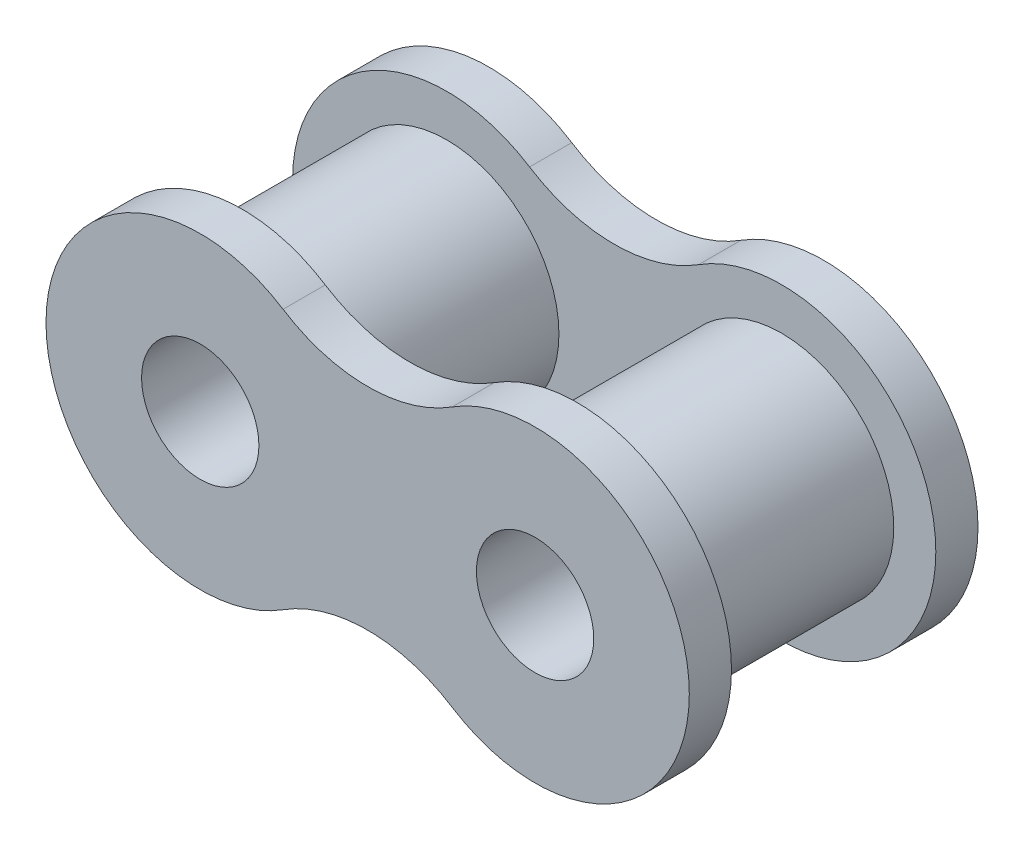
SolidWorks part; units mm, degrees
ref_plane "Front Plane" through (0, 0, 0) normal (0, 0, 1) x (1, 0, 0)
ref_plane "Top Plane" through (0, 0, 0) normal (0, 1, 0) x (1, 0, 0)
ref_plane "Right Plane" through (0, 0, 0) normal (1, 0, 0) x (0, 0, -1)
ref_axis "Axis_X" through (-19.77, 0, 0) along (1, 0, 0)
ref_axis "Axis_Y" through (0, 6.435, 0) along (0, -1, 0)
ref_axis "Axis_Z" through (0, 0, -6.0225) along (0, 0, 1)
sketch "Sketch1" plane through (0, 0, 0) normal (0, 0, 1) x (1, 0, 0)
  line L0 (0, 0) -> (-12.7, 0) construction
  line L1 (0, 4.255) -> (0, -4.255) construction
  circle A0 centre (0, 0) radius 2.225
  circle A1 centre (0, 0) radius 4.255
  circle A2 centre (-12.7, 0) radius 2.225
  circle A3 centre (-12.7, 0) radius 4.255
  dimension "FIX_31" = 4.45
  dimension "FIX_32" = 8.51
  dimension "FIX_33" = 12.7
extrude "Boss-Extrude1" add sketch "Sketch1" along normal mid plane 7.75
sketch "Sketch2" plane through (0, 0, 3.875) normal (0, 0, 1) x (1, 0, 0)
  line L0 (-12.7, 0) -> (0, 0) construction
  circle A0 centre (0, 0) radius 2.225
  circle A1 centre (-12.7, 0) radius 2.225
  arc A2 (-3.142, -4.9346) -> (-3.142, 4.9346) centre (0, 0) ccw
  arc A3 (-9.558, 4.9346) -> (-9.558, -4.9346) centre (-12.7, 0) ccw
  arc A4 (-9.558, 4.9346) -> (-3.142, 4.9346) centre (-6.35, 9.973) ccw
  arc A5 (-9.558, -4.9346) -> (-3.142, -4.9346) centre (-6.35, -9.973) cw
  dimension "FIX_35" = 4.45
  dimension "FIX_36" = 11.7
  dimension "FIX_37" = 5.973
extrude "Boss-Extrude2" add sketch "Sketch2" along normal blind 1.6
sketch "Sketch3" plane through (0, 0, -3.875) normal (0, 0, -1) x (-1, 0, 0)
  circle A0 centre (0, 0) radius 2.225
  circle A1 centre (12.7, 0) radius 2.225
  arc A2 (3.142, 4.9346) -> (3.142, -4.9346) centre (0, 0) ccw
  arc A3 (9.558, -4.9346) -> (9.558, 4.9346) centre (12.7, 0) ccw
  arc A4 (3.142, 4.9346) -> (9.558, 4.9346) centre (6.35, 9.973) ccw
  arc A5 (3.142, -4.9346) -> (9.558, -4.9346) centre (6.35, -9.973) cw
  dimension "FIX_39" = 4.45
extrude "Boss-Extrude3" add sketch "Sketch3" along normal blind 1.6
equation "\"Factor\"= 1.082532"
